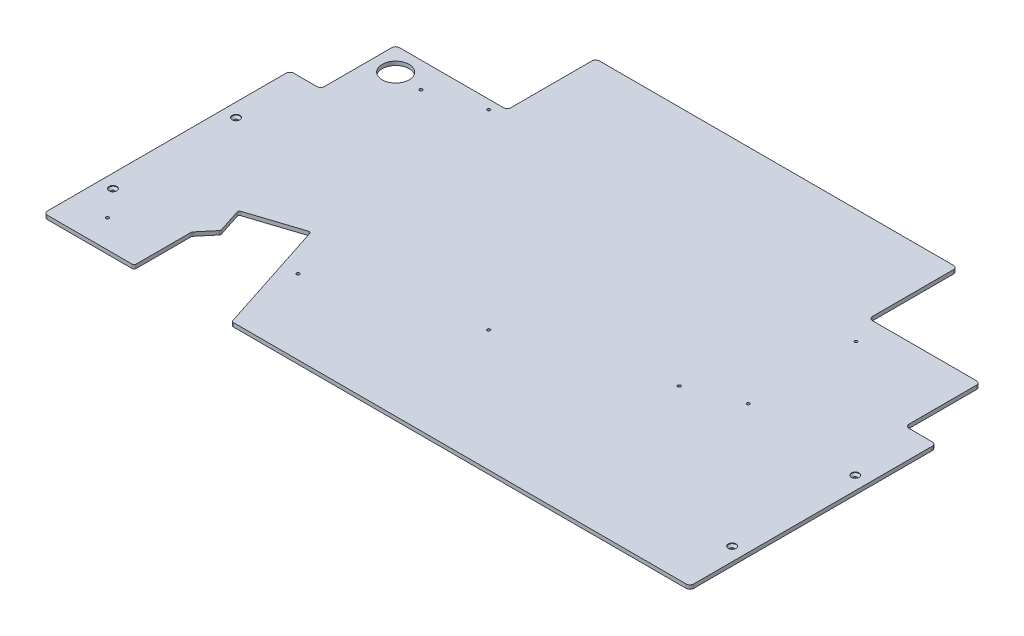
SolidWorks part; units mm, degrees
material "PE High Density"
ref_plane "Front Plane" through (0, 0, 0) normal (0, 0, 1) x (1, 0, 0)
ref_plane "Top Plane" through (0, 0, 0) normal (0, 1, 0) x (1, 0, 0)
ref_plane "Right Plane" through (0, 0, 0) normal (1, 0, 0) x (0, 0, -1)
sketch "Sketch1" plane through (0, 0, 0) normal (0, 1, 0) x (1, 0, 0)
  line L0 (1016, 406.4) -> (1066.8, 406.4)
  line L1 (0, 0) -> (1066.8, 0)
  line L2 (0, 0) -> (0, 406.4)
  line L3 (0, 406.4) -> (50.8, 406.4)
  line L4 (1066.8, 0) -> (1066.8, 406.4)
  line L6 (234.95, 530.225) -> (234.95, 676.275)
  line L7 (234.95, 676.275) -> (831.85, 676.275)
  line L8 (831.85, 530.225) -> (831.85, 676.275)
  line L12 (234.95, 530.225) -> (50.8, 530.225)
  line L13 (50.8, 406.4) -> (50.8, 530.225)
  line L16 (831.85, 530.225) -> (1016, 530.225)
  line L17 (1016, 406.4) -> (1016, 530.225)
  circle A2 centre (22.225, 92.075) radius 3.3734
  circle A3 centre (1044.575, 92.075) radius 3.3734
  circle A4 centre (22.225, 295.275) radius 3.3734
  circle A5 centre (1044.575, 295.275) radius 3.3734
  dimension "D16" = 92.075
  dimension "D11" = 6.7469
  dimension "D1" = 1066.8
  dimension "D2" = 406.4
  dimension "D3" = 596.9
  dimension "D4" = 234.95
  dimension "D5" = 676.275
  dimension "D6" = 50.8
  dimension "D7" = 50.8
  dimension "D8" = 146.05
  dimension "D9" = 146.05
  dimension "D10" = 203.2
  dimension "D15" = 22.225
  dimension "D18" = 22.225
extrude "Boss-Extrude1" add sketch "Sketch1" along normal blind 6.35
sketch "Sketch3" plane through (0, 6.35, 0) normal (0, 1, 0) x (1, 0, 0)
  line L0 (0, 0) -> (1066.8, 0) construction
  line L1 (0, 406.4) -> (0, 0) construction
  line L2 (234.95, 530.225) -> (50.8, 530.225) construction
  line L3 (50.8, 530.225) -> (50.8, 406.4) construction
  line L4 (59.3115, 45.8775) -> (771.914, 277.4161) construction
  line L5 (134.9375, 487.7489) -> (219.4864, 515.2205) construction
  line L6 (0, 406.4) -> (0, 0) construction
  circle A0 centre (134.9375, 487.7489) radius 2.4575
  circle A1 centre (219.4864, 515.2205) radius 2.4575
  circle A2 centre (59.3115, 45.8775) radius 2.4575
  circle A3 centre (296.8457, 123.057) radius 2.4574
  circle A4 centre (534.3799, 200.2365) radius 2.4575
  circle A5 centre (771.914, 277.4161) radius 2.4575
  circle A6 centre (854.075, 309.0545) radius 2.4575
  circle A7 centre (854.075, 486.8545) radius 2.4575
  circle A8 centre (88.9, 492.125) radius 22.225
  dimension "D6" = 486.8545
  dimension "D16" = 4.9149
  dimension "D17" = 44.45
  dimension "D1" = 45.8775
  dimension "D2" = 18
  dimension "D3" = 249.7582
  dimension "D4" = 249.7582
  dimension "D5" = 309.0545
  dimension "D7" = 59.3115
  dimension "D8" = 249.7582
  dimension "D9" = 88.9
  dimension "D10" = 396.875
  dimension "D11" = 854.075
  dimension "D12" = 134.9375
  dimension "D18" = 38.1
  dimension "D19" = 38.1
extrude "Cut-Extrude2" cut sketch "Sketch3" against normal through all
sketch "Sketch2" plane through (0, 6.35, 0) normal (0, 1, 0) x (1, 0, 0)
  line L0 (0, 0) -> (1066.8, 0) construction
  line L1 (310.5788, 0) -> (149.225, 0)
  line L4 (149.225, 0) -> (149.225, 95.25)
  line L5 (310.5788, 0) -> (247.65, 193.675)
  line L6 (247.65, 193.675) -> (157.0619, 164.2411)
  line L8 (0, 406.4) -> (0, 0) construction
  line L10 (157.0619, 164.2411) -> (171.0336, 121.2405)
  line L11 (171.0336, 121.2405) -> (149.225, 95.25)
  dimension "D1" = 247.65
  dimension "D2" = 149.225
  dimension "D3" = 72
  dimension "D4" = 122
  dimension "D5" = 95.25
  dimension "D6" = 193.675
  dimension "D8" = 95.25
extrude "Cut-Extrude1" cut sketch "Sketch2" against normal through all
sketch "Sketch4" plane through (0, 6.35, 0) normal (0, 1, 0) x (1, 0, 0)
  point P0 (22.225, 92.075)
  point P5 (1044.575, 92.075)
hole_wizard "CSK for 1/4 Flat Head Machine Screw1" positions "3DSketch1" profile "Sketch5" countersink size "1/4" standard "ANSI Inch" end condition through all
sketch3d "3DSketch1"
  line L0 (22.225, 6.35, -295.275) -> (22.225, 0, -295.275) construction
  line L1 (1044.575, 6.35, -295.275) -> (1044.575, 0, -295.275) construction
  point P0 (22.225, 6.35, -92.075)
  point P9 (1044.575, 6.35, -92.075)
  point P14 (22.225, 6.35, -295.275)
  point P18 (1044.575, 6.35, -295.275)
sketch "Sketch5" plane through (22.225, 6.35, -92.075) normal (1, 0, 0) x (0, 0, 1)
  line L0 (0, 0) -> (0, 6.35)
  line L1 (0, 6.35) -> (3.3782, 6.35)
  line L2 (3.3782, 6.35) -> (3.3782, 4.5369)
  line L3 (3.3782, 4.5369) -> (6.4389, 1.016)
  line L4 (6.4389, 1.016) -> (6.4389, 0)
  line L6 (6.4389, 0) -> (0, 0)
  line L7 (-3.3782, 4.5369) -> (-6.4389, 1.016) construction
  line L11 (0, -6.35) -> (0, 107.95) construction
  dimension "Thru Hole Dia." = 6.7564
  dimension "Thru Hole Depth" = 6.35
  dimension "C'Sink Dia." = 12.8778
  dimension "C'Sink Angle" = 82
  dimension "Head Clearance" = 1.016
fillet "Fillet1" radius 6.35 12 edges at (50.8, 3.175, -406.4) (0, 3.175, -406.4) (50.8, 3.175, -530.225) (234.95, 3.175, -530.225) (234.95, 3.175, -676.275) (0, 3.175, 0) (1066.8, 3.175, 0) (1066.8, 3.175, -406.4) (1016, 3.175, -406.4) (1016, 3.175, -530.225) (831.85, 3.175, -530.225) (831.85, 3.175, -676.275)
fillet "Fillet3" radius 3.175 6 edges at (310.5788, 3.175, 0) (247.65, 3.175, -193.675) (157.0619, 3.175, -164.2411) (171.0336, 3.175, -121.2405) (149.225, 3.175, -95.25) (149.225, 3.175, 0)
